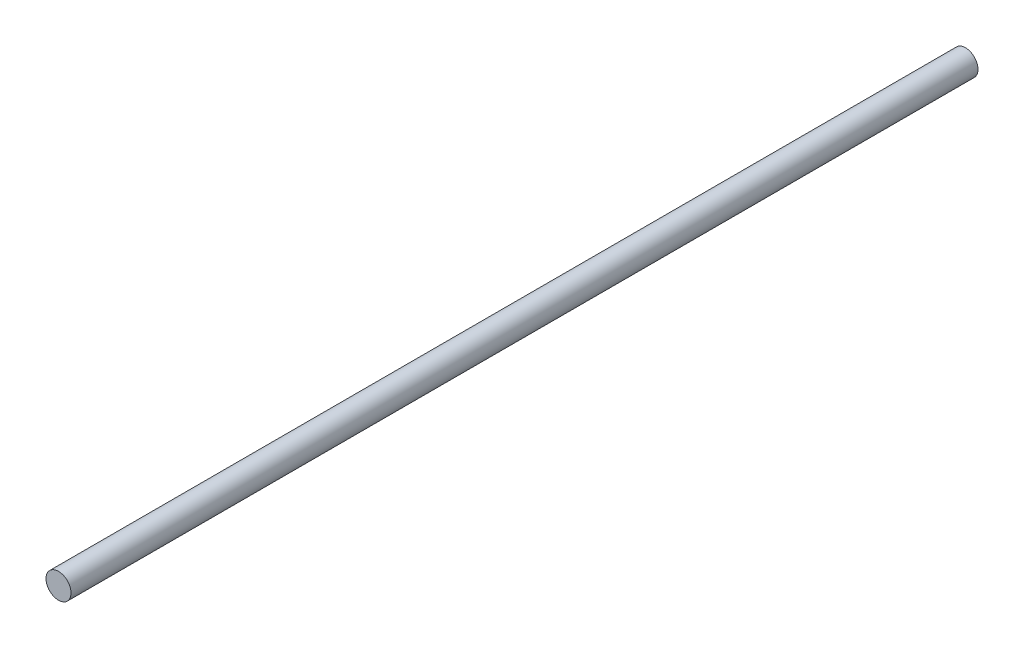
SolidWorks part; units mm, degrees
material "Plain Carbon Steel"
ref_plane "Front Plane" through (0, 0, 0) normal (0, 0, 1) x (1, 0, 0)
ref_plane "Top Plane" through (0, 0, 0) normal (0, 1, 0) x (1, 0, 0)
ref_plane "Right Plane" through (0, 0, 0) normal (1, 0, 0) x (0, 0, -1)
sketch "Sketch2" plane through (0, 0, 0) normal (0, 0, 1) x (1, 0, 0)
  circle A0 centre (0, 0) radius 3.175
  dimension "D1" = 6.35
extrude "Boss-Extrude1" add sketch "Sketch2" along normal blind 115 and the other way blind 115
